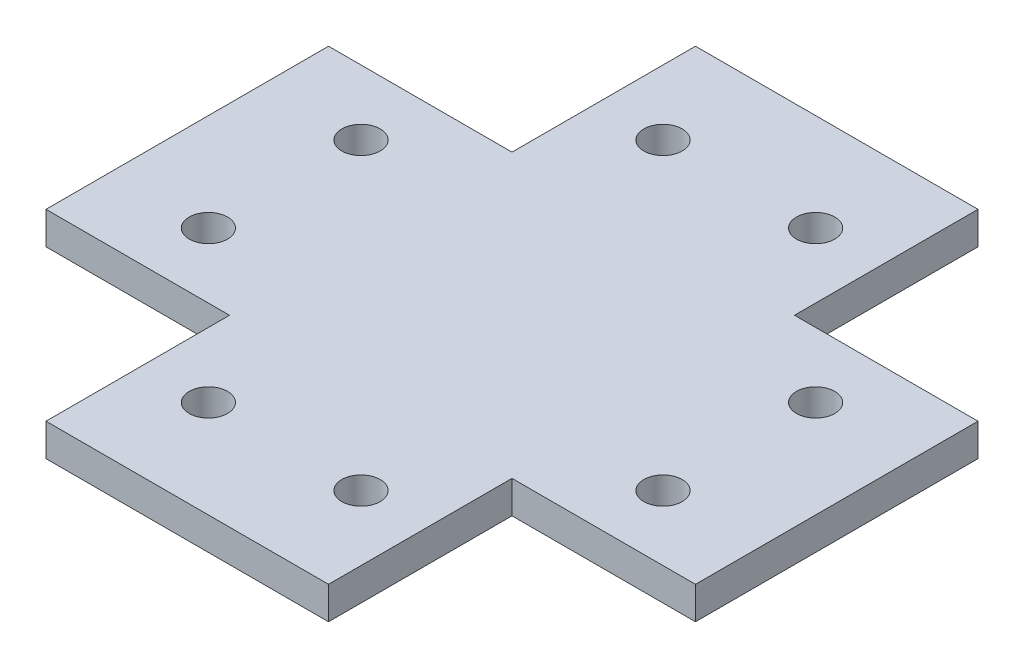
SolidWorks part; units mm, degrees
ref_plane "Front Plane" through (0, 0, 0) normal (0, 0, 1) x (1, 0, 0)
ref_plane "Top Plane" through (0, 0, 0) normal (0, 1, 0) x (1, 0, 0)
ref_plane "Right Plane" through (0, 0, 0) normal (1, 0, 0) x (0, 0, -1)
sketch "Sketch1" plane through (0, 0, 0) normal (0, 1, 0) x (1, 0, 0)
  line L1 (-25.4, 11.049) -> (25.4, 11.049)
  line L2 (-25.4, 11.049) -> (-25.4, -11.049)
  line L3 (-25.4, -11.049) -> (25.4, -11.049)
  line L4 (25.4, 11.049) -> (25.4, -11.049)
  line L5 (-25.4, 11.049) -> (25.4, -11.049) construction
  line L6 (-25.4, -11.049) -> (25.4, 11.049) construction
  line L7 (11.049, -25.4) -> (-11.049, -25.4)
  line L8 (11.049, -25.4) -> (11.049, 25.4)
  line L9 (11.049, 25.4) -> (-11.049, 25.4)
  line L10 (-11.049, -25.4) -> (-11.049, 25.4)
  line L11 (11.049, -25.4) -> (-11.049, 25.4) construction
  line L12 (11.049, 25.4) -> (-11.049, -25.4) construction
  circle A0 centre (-17.78, 5.969) radius 1.5
  circle A1 centre (-17.78, -5.969) radius 1.5
  circle A2 centre (-5.969, 17.78) radius 1.5
  circle A3 centre (5.969, 17.78) radius 1.5
  circle A4 centre (17.78, 5.969) radius 1.5
  circle A5 centre (17.78, -5.969) radius 1.5
  circle A6 centre (5.969, -17.78) radius 1.5
  circle A7 centre (-5.969, -17.78) radius 1.5
  point P0 (0, 0)
  point P6 (0, 0)
  point P15 (0, 0)
  point P16 (0, 0)
  point P17 (-6.4452, 21.0257)
  point P30 (0, 0)
  point P31 (0, 0)
  dimension "D3" = 3
  dimension "D1" = 22.098
  dimension "D2" = 50.8
  dimension "D4" = 6.731
  dimension "D5" = 5.08
  dimension "D6" = 5.08
  dimension "D7" = 4
extrude "Boss-Extrude1" add sketch "Sketch1" along normal blind 2.54 contours L3 L10 L1 L2 A1 A0 | L10 L3 L8 L1 | L10 L7 L8 L3 A7 A6 | L8 L3 L4 L1 A5 A4 | L10 L1 L8 L9 A3 A2 region at (-18.2452, 0, 0) region at (0, 0, -18.2452) region at (0, 0, 0) region at (18.2452, 0, 0) region at (0, 0, 18.2452)
